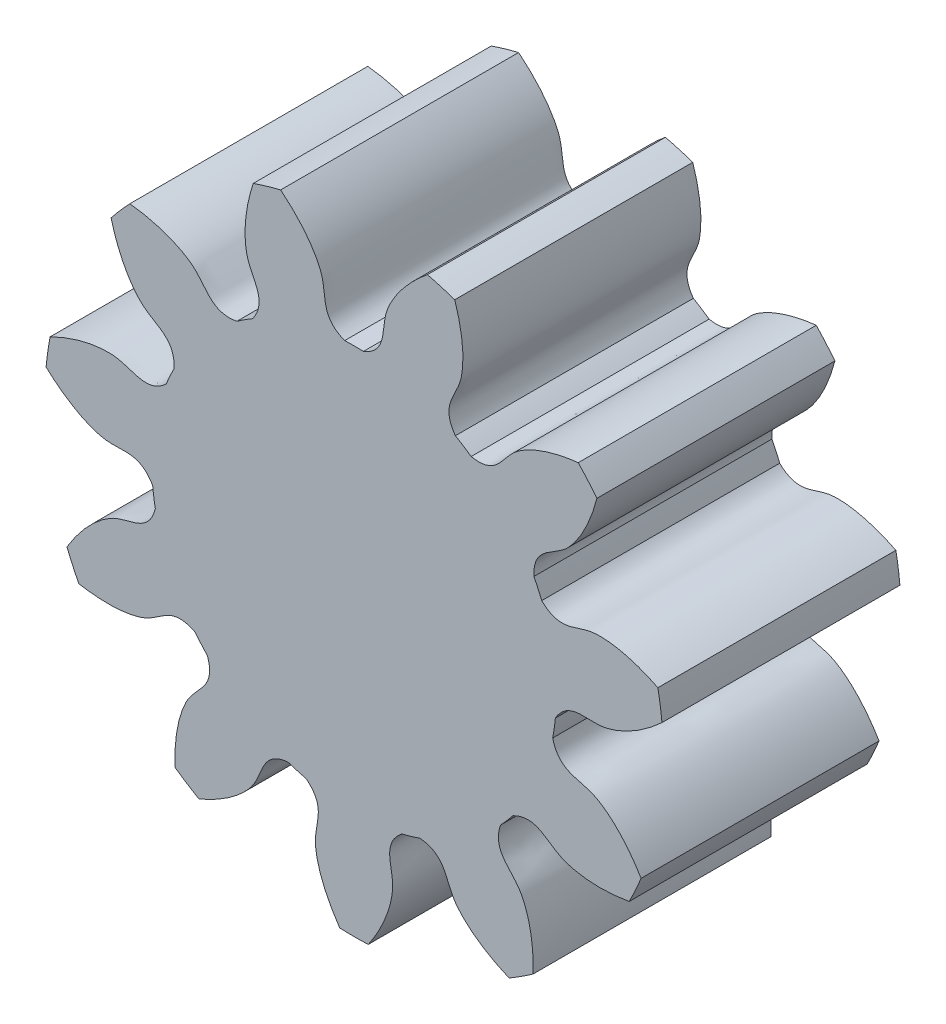
SolidWorks part; units mm, degrees
ref_plane "前视基准面" through (0, 0, 0) normal (0, 0, 1) x (1, 0, 0)
ref_plane "上视基准面" through (0, 0, 0) normal (0, 1, 0) x (1, 0, 0)
ref_plane "右视基准面" through (0, 0, 0) normal (1, 0, 0) x (0, 0, -1)
sketch "草图1" plane through (0, 0, 0) normal (0, 0, 1) x (1, 0, 0)
  circle A0 centre (0, 0) radius 6.5
extrude "凸台-拉伸1" add sketch "草图1" along normal blind 5
ref_axis "基准轴1" through (0, 0, -0.25) along (0, 0, 1)
sketch "草图2" plane through (0, 0, 0) normal (0, 0, 1) x (1, 0, 0)
  line L0 (0, 0) -> (0, 6.5) construction
  circle A0 centre (0, 0) radius 6.5 construction
  arc A1 (0.1967, 4.2454) -> (-0.1967, 4.2454) centre (0, 0) ccw
  arc A2 (3.6501, 7.2901) -> (-3.6501, 7.2901) centre (0, 0) ccw
  spline S0 degree 3 poles (0.1967, 4.2454) (0.7015, 4.4466) (0.5746, 4.858) (0.6824, 5.2075) (0.6886, 5.2262) (0.6958, 5.2467) (0.7041, 5.2689) (0.7137, 5.2929) (0.7245, 5.3187) (0.7367, 5.346) (0.7503, 5.3751) (0.7654, 5.4056) (0.7821, 5.4378) (0.8004, 5.4713) (0.8204, 5.5064) (0.8421, 5.5427) (0.8657, 5.5804) (0.8911, 5.6194) (0.9185, 5.6595) (0.9478, 5.7008) (0.9793, 5.7431) (1.0128, 5.7864) (1.0485, 5.8307) (1.0864, 5.8758) (1.1265, 5.9217) (1.169, 5.9684) (1.2138, 6.0156) (1.261, 6.0635) (1.3106, 6.1118) (1.3626, 6.1605) (1.4172, 6.2096) (1.4743, 6.2589) (1.534, 6.3084) (1.5963, 6.358) (1.6612, 6.4075) (1.7287, 6.457) (1.799, 6.5063) (1.8719, 6.5554) (1.9475, 6.6041) (2.0258, 6.6524) (2.1068, 6.7001) (2.1906, 6.7472) (2.2772, 6.7936) (2.3665, 6.8393) (2.4585, 6.884) (2.5533, 6.9277) (2.6508, 6.9704) (2.7511, 7.0119) (2.8542, 7.0521) (2.9599, 7.091) (3.0684, 7.1285) (3.1795, 7.1643) (3.2934, 7.1986) (3.45, 7.2423) (3.5695, 7.2718) (3.6501, 7.2901) knots 0 0 0 0 0.219011 0.222642 0.226699 0.231184 0.236096 0.241435 0.247201 0.253394 0.260015 0.267062 0.274537 0.282438 0.290767 0.299523 0.308706 0.318316 0.328354 0.338818 0.34971 0.361028 0.372774 0.384947 0.397547 0.410574 0.424029 0.43791 0.452219 0.466954 0.482117 0.497707 0.513724 0.530168 0.547039 0.564338 0.582063 0.600216 0.618795 0.637802 0.657236 0.677097 0.697385 0.718101 0.739243 0.760813 0.782809 0.805233 0.828084 0.851362 0.875067 0.8992 0.923759 0.948746 1 1 1 1
  spline S1 degree 3 poles (-0.1967, 4.2454) (-0.7015, 4.4466) (-0.5746, 4.858) (-0.6824, 5.2075) (-0.6886, 5.2262) (-0.6958, 5.2467) (-0.7041, 5.2689) (-0.7137, 5.2929) (-0.7245, 5.3187) (-0.7367, 5.346) (-0.7503, 5.3751) (-0.7654, 5.4056) (-0.7821, 5.4378) (-0.8004, 5.4713) (-0.8204, 5.5064) (-0.8421, 5.5427) (-0.8657, 5.5804) (-0.8911, 5.6194) (-0.9185, 5.6595) (-0.9478, 5.7008) (-0.9793, 5.7431) (-1.0128, 5.7864) (-1.0485, 5.8307) (-1.0864, 5.8758) (-1.1265, 5.9217) (-1.169, 5.9684) (-1.2138, 6.0156) (-1.261, 6.0635) (-1.3106, 6.1118) (-1.3626, 6.1605) (-1.4172, 6.2096) (-1.4743, 6.2589) (-1.534, 6.3084) (-1.5963, 6.358) (-1.6612, 6.4075) (-1.7287, 6.457) (-1.799, 6.5063) (-1.8719, 6.5554) (-1.9475, 6.6041) (-2.0258, 6.6524) (-2.1068, 6.7001) (-2.1906, 6.7472) (-2.2772, 6.7936) (-2.3665, 6.8393) (-2.4585, 6.884) (-2.5533, 6.9277) (-2.6508, 6.9704) (-2.7511, 7.0119) (-2.8542, 7.0521) (-2.9599, 7.091) (-3.0684, 7.1285) (-3.1795, 7.1643) (-3.2934, 7.1986) (-3.45, 7.2423) (-3.5695, 7.2718) (-3.6501, 7.2901) knots 0 0 0 0 0.219011 0.222642 0.226699 0.231184 0.236096 0.241435 0.247201 0.253394 0.260015 0.267062 0.274537 0.282438 0.290767 0.299523 0.308706 0.318316 0.328354 0.338818 0.34971 0.361028 0.372774 0.384947 0.397547 0.410574 0.424029 0.43791 0.452219 0.466954 0.482117 0.497707 0.513724 0.530168 0.547039 0.564338 0.582063 0.600216 0.618795 0.637802 0.657236 0.677097 0.697385 0.718101 0.739243 0.760813 0.782809 0.805233 0.828084 0.851362 0.875067 0.8992 0.923759 0.948746 1 1 1 1
extrude "切除-拉伸1" cut sketch "草图2" along normal through all
pattern_circular "阵列(圆周)1" count 11 every 32.727 about axis through (0, 0, -0.25) along (0, 0, 1) of "切除-拉伸1"
sketch "草图3" plane through (0, 0, 0) normal (0, 0, 1) x (1, 0, 0)
  circle A0 centre (0, 0) radius 5.5 construction
  dimension "Dn" = 11
